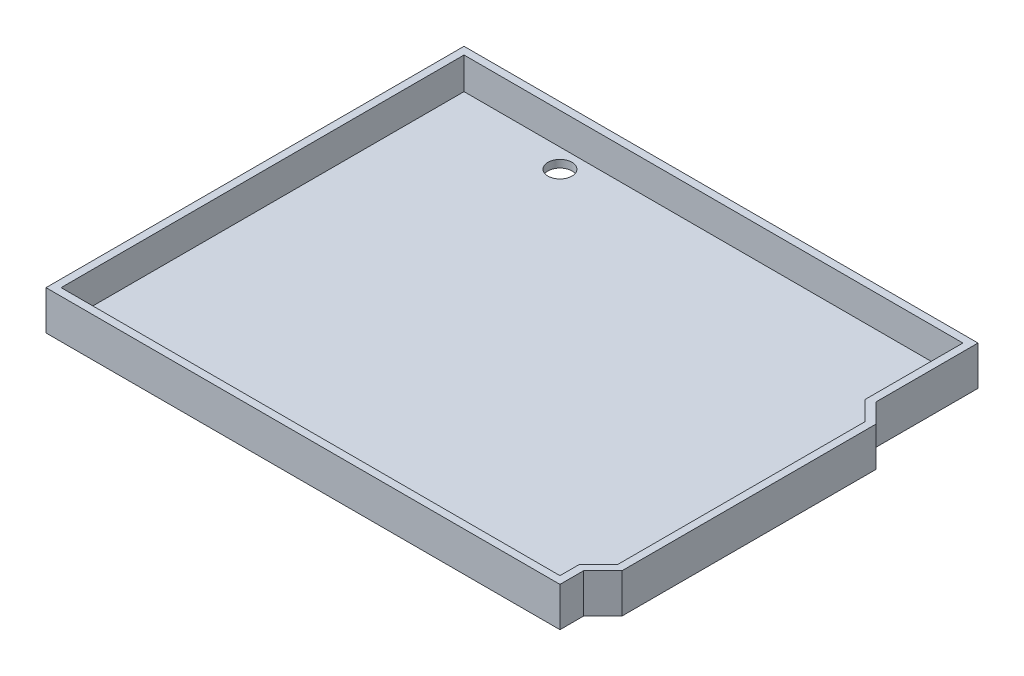
SolidWorks part; units mm, degrees
ref_plane "Front Plane" through (0, 0, 0) normal (0, 0, 1) x (1, 0, 0)
ref_plane "Top Plane" through (0, 0, 0) normal (0, 1, 0) x (1, 0, 0)
ref_plane "Right Plane" through (0, 0, 0) normal (1, 0, 0) x (0, 0, -1)
sketch "Sketch1" plane through (0, 0, 0) normal (0, 1, 0) x (1, 0, 0)
  line L0 (33.02, -26.67) -> (33.02, -24.13)
  line L1 (-33.02, 26.67) -> (33.02, 26.67)
  line L2 (-33.02, 26.67) -> (-33.02, -26.67)
  line L3 (-33.02, -26.67) -> (33.02, -26.67)
  line L4 (33.02, 26.67) -> (33.02, -26.67) construction
  line L5 (-33.02, 26.67) -> (33.02, -26.67) construction
  line L6 (-33.02, -26.67) -> (33.02, 26.67) construction
  line L11 (33.02, -24.13) -> (33.02, -21.59) construction
  line L12 (33.02, -24.13) -> (35.56, -21.59)
  line L13 (33.02, 26.67) -> (33.02, 13.72)
  line L14 (35.56, -21.59) -> (35.56, 11.18)
  line L15 (33.02, 13.72) -> (35.56, 11.18)
  line L16 (34.02, 14.1342) -> (36.56, 11.5942)
  line L17 (36.56, -22.0042) -> (36.56, 11.5942)
  line L18 (34.02, -24.5442) -> (36.56, -22.0042)
  line L19 (34.02, -27.67) -> (34.02, -24.5442)
  line L20 (-34.02, -27.67) -> (34.02, -27.67)
  line L21 (-34.02, 27.67) -> (-34.02, -27.67)
  line L22 (-34.02, 27.67) -> (34.02, 27.67)
  line L23 (34.02, 27.67) -> (34.02, 14.1342)
  circle A0 centre (33.02, -19.05) radius 1.59
  circle A1 centre (33.02, 8.89) radius 1.59
  circle A2 centre (-17.78, 24.13) radius 1.59
  circle A3 centre (-19.05, -24.13) radius 1.59
  point P0 (0, 0)
  point P6 (0, 0)
  dimension "D9" = 3.18
  dimension "D1" = 66.04
  dimension "D2" = 53.34
  dimension "D3" = 2.54
  dimension "D4" = 2.54
  dimension "D5" = 1
  dimension "D6" = 12.95
  dimension "D7" = 32.77
  dimension "D8" = 135
  dimension "D10" = 7.62
  dimension "D11" = 27.94
  dimension "D12" = 15.24
  dimension "D13" = 2.54
  dimension "D14" = 2.54
  dimension "D15" = 13.97
extrude "Boss-Extrude1" add sketch "Sketch1" against normal blind 5.2 contours L15 L13 L1 L2 L3 L0 L12 L14 | L23 L22 L21 L20 L19 L18 L17 L16 L13 L15 L14 L12 L0 L3 L2 L1 region at (0.7934, 0, 0.1078) region at (34.6558, 0, -12.23)
extrude "Cut-Extrude2" cut sketch "Sketch1<5>" against normal blind 4.2 contours L15 L13 L1 L2 L3 L0 L12 L14 A3 A2 A1 A0 region at (0.7934, 0, 0.1078)
sketch "Sketch1<5>" plane through (0, 0, 0) normal (0, 1, 0) x (1, 0, 0) same geometry as "Sketch1"
